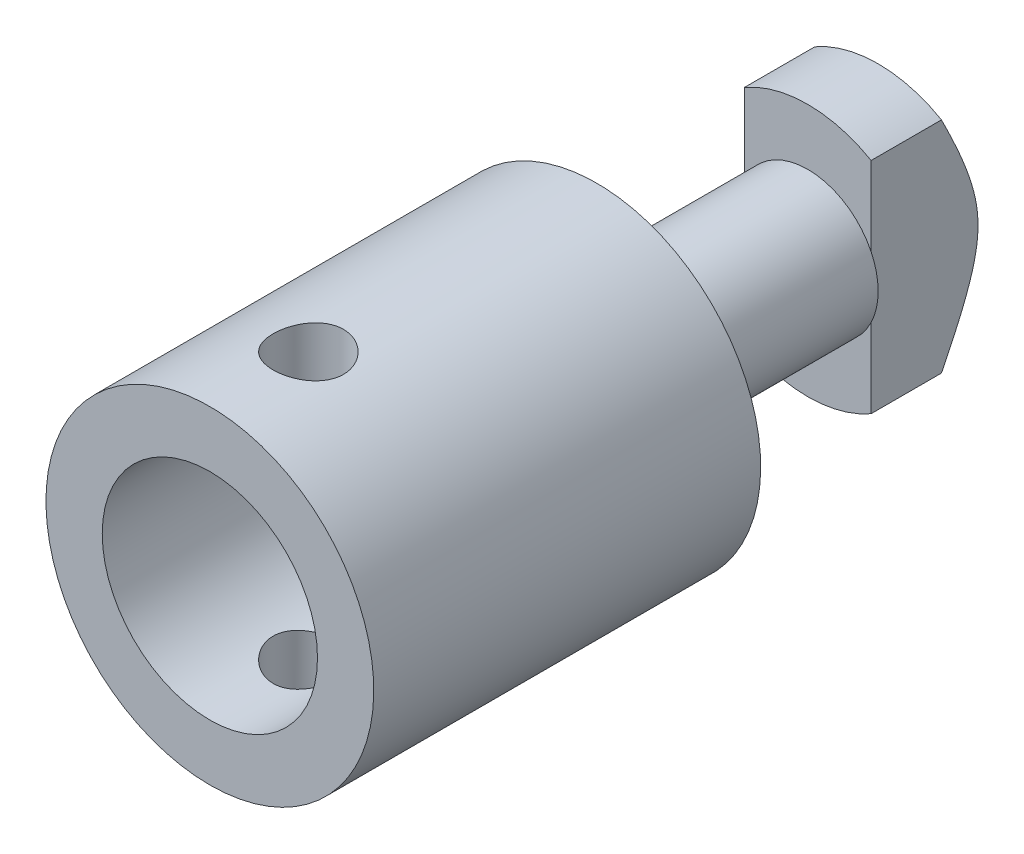
SolidWorks part; units mm, degrees
material "AISI Type 316L stainless steel"
ref_plane "Front" through (0, 0, 0) normal (0, 0, 1) x (1, 0, 0)
ref_plane "Top" through (0, 0, 0) normal (0, 1, 0) x (1, 0, 0)
ref_plane "Right" through (0, 0, 0) normal (1, 0, 0) x (0, 0, -1)
ref_axis "X" through (-80.9, 0, 0) along (1, 0, 0)
ref_axis "Y" through (0, -50, 0) along (0, 1, 0)
ref_axis "Z" through (0, 0, -80.9) along (0, 0, 1)
sketch "Sketch1" plane through (0, 0, 0) normal (1, 0, 0) x (0, 0, -1)
  line L0 (-2.9655, 0) -> (2.9655, 0) construction
  line L1 (0, 2.33) -> (5.5, 2.33)
  line L2 (5.5, 2.33) -> (5.5, 1)
  line L3 (5.5, 1) -> (8.5, 1)
  line L4 (8.5, 1) -> (8.5, 1.8)
  line L5 (8.5, 1.8) -> (9.5, 1.8)
  line L8 (9.5, 1.8) -> (10.5392, 0)
  line L10 (0, 1.53) -> (0, 2.33)
  line L11 (0, 1.53) -> (4, 1.53)
  line L12 (4, 1.53) -> (4, 0)
  line L13 (4, 0) -> (10.5392, 0)
  dimension "D1" = 3.06
  dimension "D2" = 0.8
  dimension "D3" = 4
  dimension "D4" = 1.5
  dimension "D5" = 30
  dimension "D6" = 2
  dimension "D7" = 1
  dimension "D8" = 0.8
  dimension "D9" = 3
revolve "Revolve1" add sketch "Sketch1" angle 360 about L0
sketch "Sketch2" plane through (0, 0, 0) normal (0, 0, 1) x (1, 0, 0)
  line L0 (0.9, 5) -> (0.9, -5)
  line L1 (0.9, -5) -> (5.9, -5)
  line L2 (5.9, -5) -> (5.9, 5)
  line L3 (5.9, 5) -> (0.9, 5)
  line L4 (-5.9, 5) -> (-5.9, -5)
  line L5 (-5.9, -5) -> (-0.9, -5)
  line L6 (-0.9, -5) -> (-0.9, 5)
  line L7 (-0.9, 5) -> (-5.9, 5)
  line L8 (0, 0) -> (0.9, 0) construction
  line L9 (0, 0) -> (-0.9, 0) construction
  dimension "D1" = 1.8
  dimension "D2" = 10
  dimension "D3" = 5
extrude "Cut-Extrude1" cut sketch "Sketch2" against normal through all from surface starting at face at (0, -1, -8.5)
sketch "Sketch3" plane through (0, 0, 0) normal (0, 1, 0) x (1, 0, 0)
  line L0 (0, 1.4) -> (0, 0) construction
  circle A0 centre (0, 1.4) radius 0.5
  dimension "D1" = 1
  dimension "D2" = 1.4
extrude "Cut-Extrude2" cut sketch "Sketch3" against normal through all both and the other way through all
